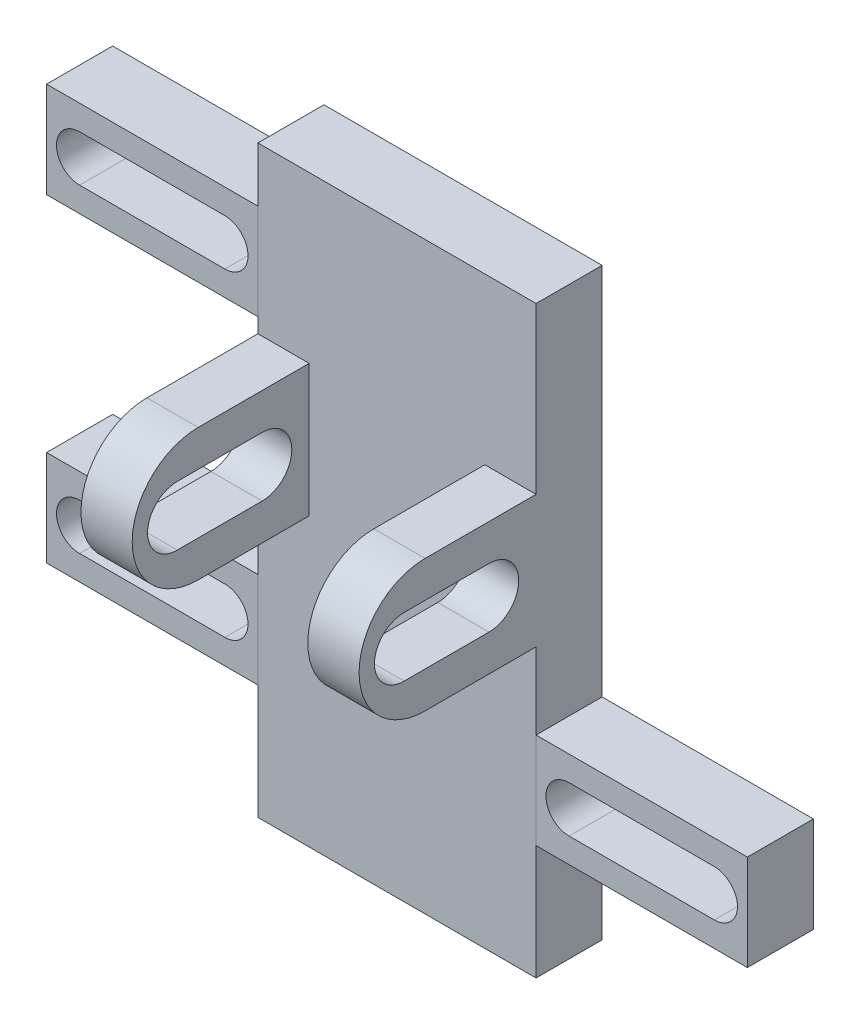
SolidWorks part; units mm, degrees
ref_plane "Front Plane" through (0, 0, 0) normal (0, 0, 1) x (1, 0, 0)
ref_plane "Top Plane" through (0, 0, 0) normal (0, 1, 0) x (1, 0, 0)
ref_plane "Right Plane" through (0, 0, 0) normal (1, 0, 0) x (0, 0, -1)
sketch "Sketch1" plane through (0, 0, 0) normal (0, 0, 1) x (1, 0, 0)
  line L0 (4692.3212, -62.8445) -> (4650.9212, -62.8445) construction
  line L1 (4661.0828, -18.6148) -> (4682.1433, -18.6148)
  line L2 (4661.0828, -18.6148) -> (4661.0828, -62.8445)
  line L3 (4661.0828, -62.8445) -> (4682.1433, -62.8445)
  line L4 (4682.1433, -18.6148) -> (4682.1433, -62.8445)
  line L5 (4661.0828, -27.1456) -> (4658.9212, -27.1456) construction
  line L6 (4658.9212, -12.4285) -> (4658.9212, -50.5381) construction
  line L7 (4682.1433, -34.3161) -> (4684.3037, -34.2412) construction
  line L8 (4684.3037, -50.5381) -> (4684.3037, -12.4285) construction
extrude "Boss-Extrude1" add sketch "Sketch1" along normal blind 5
sketch "Sketch2" plane through (0, 0, 0) normal (0, 0, -1) x (-1, 0, 0)
  line L0 (-4671.6212, -59.6913) -> (-4671.6212, -53.6913) construction
  line L1 (-4664.1212, -59.6913) -> (-4679.1212, -59.6913) construction
  line L2 (-4679.1212, -53.6913) -> (-4664.1212, -53.6913) construction
  line L4 (-4674.1212, -53.8163) -> (-4669.1212, -53.8163)
  line L5 (-4674.1212, -53.8163) -> (-4674.1212, -59.5663)
  line L6 (-4674.1212, -59.5663) -> (-4669.1212, -59.5663)
  line L7 (-4669.1212, -53.8163) -> (-4669.1212, -59.5663)
  line L8 (-4674.1212, -53.8163) -> (-4669.1212, -59.5663) construction
  line L9 (-4674.1212, -59.5663) -> (-4669.1212, -53.8163) construction
  point P6 (-4671.6212, -56.6913)
  dimension "D1" = 5.75
  dimension "D2" = 5
extrude "Boss-Extrude2" add sketch "Sketch2" along normal blind 8
sketch "Sketch4" plane through (4661.0828, 0, 0) normal (-1, 0, 0) x (0, 0, 1)
  line L3 (5, -18.6148) -> (5, -62.8445) construction
  line L4 (13.4005, -31.1292) -> (5, -31.1292)
  line L6 (13.4005, -41.1292) -> (5, -41.1292)
  line L7 (5, -31.1292) -> (5, -41.1292)
  arc A0 (13.4005, -41.1292) -> (13.4005, -31.1292) centre (13.4005, -36.1292) ccw
  dimension "D1" = 5
extrude "Boss-Extrude3" add sketch "Sketch4" against normal blind 3.8801
sketch "Sketch5" plane through (4664.9629, 0, 0) normal (1, 0, 0) x (0, 0, -1)
  line L0 (-14.9864, -36.1292) -> (-8.5634, -36.1292) construction
  line L1 (-14.9864, -33.8792) -> (-8.5634, -33.8792)
  line L2 (-14.9864, -38.3792) -> (-8.5634, -38.3792)
  line L3 (-13.4005, -36.1292) -> (-8.9343, -36.1292) construction
  arc A1 (-14.9864, -33.8792) -> (-14.9864, -38.3792) centre (-14.9864, -36.1292) ccw
  arc A2 (-8.5634, -38.3792) -> (-8.5634, -33.8792) centre (-8.5634, -36.1292) ccw
  point P3 (-11.7749, -36.1292)
  dimension "D1" = 2.25
  dimension "D2" = 1.6257
  dimension "D3" = 4.8372
extrude "Cut-Extrude1" cut sketch "Sketch5" against normal blind 8
ref_plane "Plane1" through (4671.6131, 0, 0) normal (-1, 0, 0) x (0, 0, 1)
mirror "Mirror2" about plane through (4671.6131, 0, 0) normal (-1, 0, 0) of "Cut-Extrude1", "Boss-Extrude3"
sketch "Sketch6" plane through (0, 0, 5) normal (0, 0, 1) x (1, 0, 0)
  line L0 (4688.3131, -48.9131) -> (4688.3131, -52.1631) construction
  line L1 (4682.1433, -46.9131) -> (4698.1433, -46.9131)
  line L2 (4682.1433, -46.9131) -> (4682.1433, -54.1631)
  line L3 (4682.1433, -54.1631) -> (4698.1433, -54.1631)
  line L4 (4698.1433, -46.9131) -> (4698.1433, -54.1631)
  line L5 (4658.9131, -50.5381) -> (4684.2955, -50.5381) construction
  line L6 (4688.3131, -52.1631) -> (4688.3131, -54.1631) construction
  line L7 (4688.3131, -48.9131) -> (4688.3131, -46.9131) construction
  line L8 (4658.4131, -50.5381) -> (4684.8131, -50.5381) construction
  line L9 (4695.6433, -50.5381) -> (4684.6433, -50.5381) construction
  line L10 (4695.6433, -52.2881) -> (4684.6433, -52.2881)
  line L11 (4695.6433, -48.7881) -> (4684.6433, -48.7881)
  line L12 (4686.6881, -50.5381) -> (4689.9381, -50.5381) construction
  line L13 (4695.6433, -52.2881) -> (4698.1433, -52.2881) construction
  line L14 (4682.1433, -62.8445) -> (4682.1433, -41.1292) construction
  line L15 (4661.0828, -18.6148) -> (4661.0828, -31.1292) construction
  line L16 (4682.1433, -18.6148) -> (4661.0828, -18.6148) construction
  arc A1 (4695.6433, -52.2881) -> (4695.6433, -48.7881) centre (4695.6433, -50.5381) ccw
  arc A2 (4684.6433, -48.7881) -> (4684.6433, -52.2881) centre (4684.6433, -50.5381) ccw
  circle A3 centre (4688.3131, -50.5381) radius 1.625 construction
  point P18 (4690.1433, -50.5381)
  dimension "D2" = 16
  dimension "D3" = 11
  dimension "D1" = 1.75
  dimension "D4" = 2.5
  dimension "D5" = 27.2303
  dimension "D6" = 28.2983
  dimension "D7" = 35.5483
extrude "Boss-Extrude4" add sketch "Sketch6" against normal blind 5 separate body
ref_plane "Plane2" through (4671.6131, 0, 0) normal (-1, 0, 0) x (0, 0, 1)
mirror "Mirror3" about plane through (4671.6131, 0, 0) normal (-1, 0, 0) of bodies 107
ref_plane "Plane3" through (0, -24.872, 0) normal (0, -1, 0) x (-1, 0, 0)
sketch "Sketch9" plane through (0, 0, 5) normal (0, 0, 1) x (1, 0, 0)
  line L0 (4671.6131, -62.8445) -> (4671.6131, -18.6148) construction
  line L1 (4661.0828, -62.8445) -> (4682.1433, -62.8445) construction
  line L2 (4682.1433, -18.6148) -> (4661.0828, -18.6148) construction
  line L3 (4671.6131, -40.7297) -> (4677.5932, -40.7297) construction
ref_plane "Plane4" through (0, -40.7297, 0) normal (0, -1, 0) x (-1, 0, 0)
sketch "Sketch10" plane through (0, 0, 5) normal (0, 0, 1) x (1, 0, 0)
  line L0 (4654.9131, -26.3852) -> (4654.9131, -50.5381) construction
  line L1 (4654.9131, -38.4617) -> (4652.351, -38.4617) construction
ref_plane "Plane5" through (0, -38.4617, 0) normal (0, -1, 0) x (-1, 0, 0)
mirror "Mirror4" about plane through (0, -38.4617, 0) normal (0, -1, 0) of bodies 109 107
sketch "Sketch11" plane through (0, 0, 5) normal (0, 0, 1) x (1, 0, 0)
  line L1 (4682.1433, -22.7602) -> (4698.1433, -22.7602)
  line L2 (4682.1433, -22.7602) -> (4682.1433, -30.0102)
  line L3 (4682.1433, -30.0102) -> (4698.1433, -30.0102)
  line L4 (4698.1433, -22.7602) -> (4698.1433, -30.0102)
extrude "Cut-Extrude2" cut sketch "Sketch11" against normal up to vertex (5 mm away) up to point (4682.1433, -22.7602, 0)
